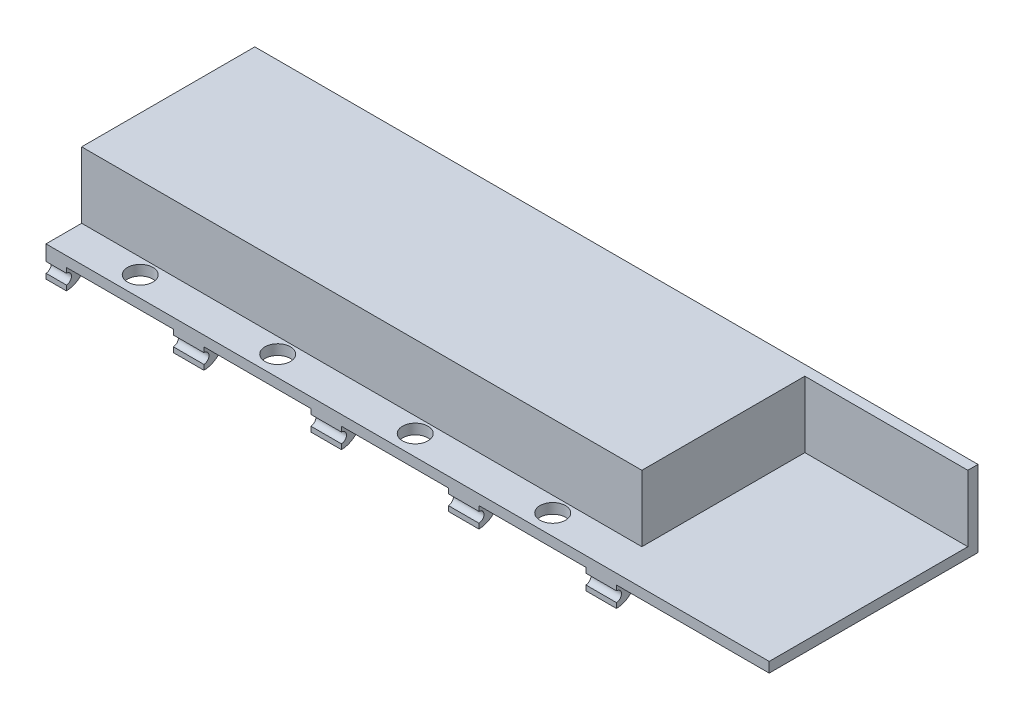
SolidWorks part; units mm, degrees
ref_plane "前视基准面" through (0, 0, 0) normal (0, 0, 1) x (1, 0, 0)
ref_plane "上视基准面" through (0, 0, 0) normal (0, 1, 0) x (1, 0, 0)
ref_plane "右视基准面" through (0, 0, 0) normal (1, 0, 0) x (0, 0, -1)
sketch "草图3" plane through (0, 0, 0) normal (0, 1, 0) x (1, 0, 0)
  line L0 (0, 0) -> (-71, 0)
  line L1 (-71, 0) -> (-71, 41)
  line L2 (-71, 41) -> (71, 41)
  line L3 (71, 41) -> (71, 0)
  line L4 (0, 0) -> (71, 0)
extrude "凸台-拉伸1" add sketch "草图3" along normal blind 15
sketch "草图4" plane through (0, 0, 0) normal (0, 1, 0) x (1, 0, 0)
  line L0 (-69, 39) -> (-69, 9)
  line L2 (-69, 9) -> (-44, 9)
  line L3 (-69, 39) -> (-44, 39)
  line L4 (-44, 9) -> (-44, 39)
extrude "切除-拉伸2" cut sketch "草图4" along normal offset from surface (13 mm away) 2 up to face at (0, 15, -20.5)
ref_axis "基准轴1" through (-71, 15, 0) along (1, 0, 0)
pattern_linear "阵列(线性)1" count 4 spacing 27 along (1, 0, 0) of "切除-拉伸2"
sketch "草图6" plane through (71, 0, 0) normal (1, 0, 0) x (0, 0, -1)
  line L0 (0, 15) -> (7, 15)
  line L1 (0, 15) -> (41, 15) construction
  line L2 (7, 15) -> (7, 2)
  line L3 (7, 2) -> (0, 2)
  line L4 (0, 15) -> (0, 0) construction
  line L5 (0, 2) -> (0, 15)
  dimension "D1" = 7
extrude "切除-拉伸3" cut sketch "草图6" against normal through all
sketch "草图7" plane through (71, 0, 0) normal (1, 0, 0) x (0, 0, -1)
  line L0 (0, 0) -> (4, 0)
  line L1 (0, 0) -> (0, -4)
  line L2 (0, 2) -> (0, 0) construction
  arc A0 (0, -4) -> (4, 0) centre (0, 0) ccw
extrude "凸台-拉伸2" add sketch "草图7" against normal up to surface (142 mm away) up to face at (-71, 5.6667, -16)
sketch "草图8" plane through (71, 0, 0) normal (1, 0, 0) x (0, 0, -1)
  line L0 (0, -1) -> (0, -2)
  line L4 (0, 2) -> (0, -4) construction
  line L5 (0, -2) -> (0, -3)
  arc A0 (0, -3) -> (0, -1) centre (0, -2) ccw
extrude "切除-拉伸4" cut sketch "草图8" against normal through all
sketch "草图14" plane through (0, 0, 0) normal (0, 0, 1) x (1, 0, 0)
  line L0 (-67, -4) -> (-46, -4)
  line L1 (-46, 0) -> (-67, 0)
  line L3 (-71, -4) -> (71, -4) construction
  line L5 (-67, -4) -> (-67, 0)
  line L9 (-46, 0) -> (-46, -4)
extrude "切除-拉伸7" cut sketch "草图14" against normal through all
pattern_linear "阵列(线性)3" count 5 spacing 27 along (1, 0, 0) of "切除-拉伸7"
sketch "草图16" plane through (0, 0, 0) normal (0, 0, 1) x (1, 0, 0)
  line L0 (71, -1) -> (71, 0)
  line L1 (71, -4) -> (71, -1)
  line L2 (71, 2) -> (71, -1) construction
  line L3 (71, 0) -> (42.1782, 0)
  line L4 (42.1782, -4) -> (71, -4)
  line L8 (42.1782, -4) -> (42.1782, 0)
extrude "切除-拉伸8" cut sketch "草图16" against normal through all
sketch "草图17" plane through (0, 0, 0) normal (0, -1, 0) x (1, 0, 0)
  circle A0 centre (-56.5, -4) radius 2.5
extrude "切除-拉伸9" cut sketch "草图17" against normal through all
pattern_linear "阵列(线性)4" count 4 spacing 27 along (1, 0, 0) of "切除-拉伸9"
ref_plane "基准面13" through (0, 0, 0) normal (0, 0, 1) x (1, 0, 0)
sketch "草图21" plane through (71, 0, 0) normal (1, 0, 0) x (0, 0, -1)
  line L0 (7, 15) -> (7, 2)
  line L1 (7, 2) -> (39, 2)
  line L4 (39, 2) -> (39, 15)
  line L5 (7, 15) -> (41, 15) construction
  line L6 (39, 15) -> (7, 15)
extrude "切除-拉伸11" cut sketch "草图21" against normal offset from surface (32 mm away) 2 up to face at (37, 6.5, -24)
sketch "草图23" plane through (0, 0, -41) normal (0, 0, -1) x (-1, 0, 0)
  line L0 (71, 0) -> (69.7009, 0)
  line L1 (-71, 0) -> (71, 0) construction
  line L2 (69.7009, 0) -> (57.2009, 0)
